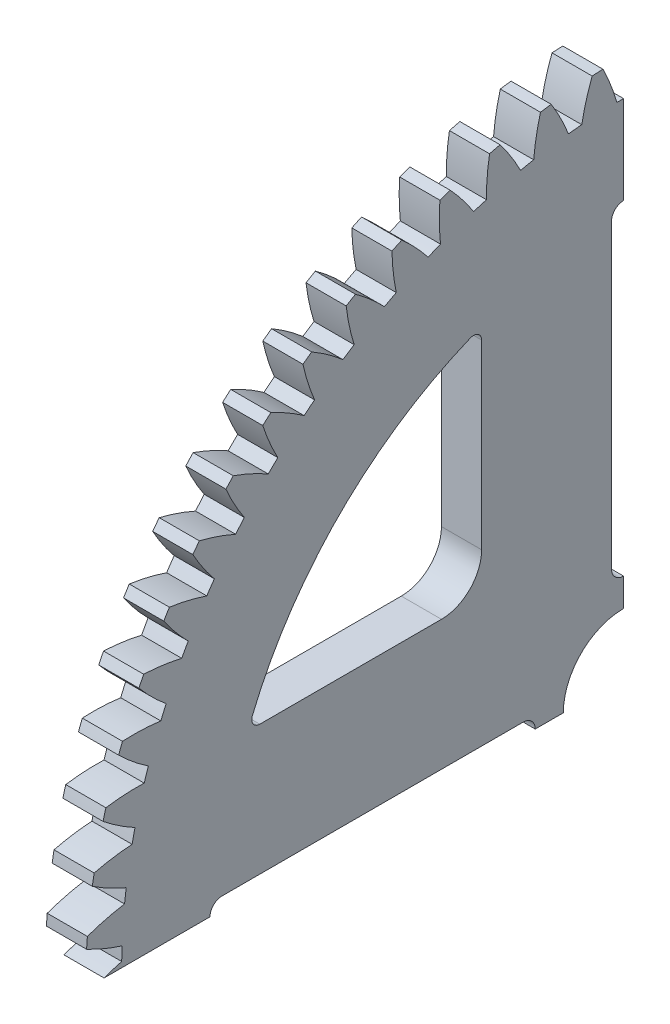
SolidWorks part; units mm, degrees
material "ABS"
ref_plane "Plane1" through (0, 0, 0) normal (0, 0, 1) x (1, 0, 0)
ref_plane "Plane2" through (0, 0, 0) normal (0, 1, 0) x (1, 0, 0)
ref_plane "Plane3" through (0, 0, 0) normal (1, 0, 0) x (0, 0, -1)
sketch "HoldingSke" plane through (0, 0, 0) normal (0, 1, 0) x (1, 0, 0)
  line L0 (0, 0) -> (0.1057, -0.2266)
  line L1 (-15, 0) -> (100, 0) construction
  line L2 (0, 0) -> (-2.1039, 2.3779)
  line L3 (0, 0) -> (-11.863, 4.5341)
  line L4 (0, 0) -> (3.6497, 7.8269)
  line L5 (0, 0) -> (-46.8476, -17.4728)
  line L6 (0, 0) -> (-8.2896, -5.593)
  line L7 (-2.1039, 2.3779) -> (8.6586, 51.2059)
  line L8 (-76.2, 54.61) -> (-74.8, 54.61)
  line L9 (-71.009, 38.7566) -> (-53.1078, 45.2721)
  line L10 (-76.2, 71.12) -> (104.1128, 71.12)
  line L11 (0, 0) -> (-10, 0)
  line L12 (-76.2, 101.6) -> (-76.073, 101.6)
  line L13 (24.9733, 27.94) -> (52.9518, 28.4284)
  line L14 (24.9733, 27.94) -> (24.9743, 27.94)
  line L15 (24.9733, 27.94) -> (100.4006, 29.5858)
  line L16 (-63.627, -4) -> (-12.827, -4)
  circle A0 centre (0, 0) radius 4
  circle A1 centre (0, 0) radius 6
  circle A2 centre (0, 0) radius 6
  circle A3 centre (0, 0) radius 4
  dimension "Num_teeth" = 65
  dimension "Pitch_radius" = 180.3128
  dimension "Width" = 10
  dimension "Thickness" = 10
sketch "BasProSke" plane through (0, 0, 0) normal (0, 1, 0) x (1, 0, 0)
  line L0 (-10, 0) -> (60, 0) construction
  line L1 (0, 0) -> (0, 134)
  line L2 (0, 0) -> (10, 0)
  line L3 (10, 0) -> (10, 134)
  line L4 (10, 134) -> (0, 134)
  dimension "Thickness" = 10
  dimension "Diameter" = 268
revolve "Base-Revolve" add sketch "BasProSke" angle 360 about L0
sketch "TooCutSke" plane through (0, 0, 0) normal (1, 0, 0) x (0, 0, -1)
  line L1 (0, 0) -> (0, 107) construction
  line L2 (0, 0) -> (-3.3635, 129.9565) construction
  line L3 (0, 0) -> (-12.5583, 259.6309) construction
  line L4 (-3.3635, 129.9565) -> (-6.2792, 129.8155) construction
  arc A0 (1.6677, 124.9879) -> (-1.6677, 124.9879) centre (0, 0) ccw
  arc A1 (5.1425, 133.9267) -> (-5.1425, 133.9267) centre (0, 0) ccw
  circle A2 centre (0, 0) radius 130 construction
  circle A3 centre (0, 0) radius 122.16 construction
  arc A4 (-1.6677, 124.9879) -> (-5.1425, 133.9267) centre (-51.6653, 110.6968) ccw
  arc A5 (5.1425, 133.9267) -> (1.6677, 124.9879) centre (51.6653, 110.6968) ccw
extrude "ToothCut" cut sketch "TooCutSke" along normal through all
fillet "Breaks" [suppressed] radius 0.08
fillet "RootFillets" [suppressed] radius 1.001
pattern_circular "TeethCuts" count 65 every 5.538 about axis through (-10, 0, 0) along (1, 0, 0) of "ToothCut", "RootFillets", "Breaks"
sketch "HubNeaOneSke" plane through (0, 0, 0) normal (-1, 0, 0) x (0, 0, 1)
  circle A0 centre (0, 0) radius 6
  dimension "Diameter" = 12
extrude "HubNearOne" add sketch "HubNeaOneSke" along normal blind 40.0001
sketch "HubNeaBotSke" plane through (0, 0, 0) normal (-1, 0, 0) x (0, 0, 1)
  circle A0 centre (0, 0) radius 6
  dimension "Diameter" = 12
extrude "HubNearBoth" [suppressed] add sketch "HubNeaBotSke" along normal blind 20
ref_plane "FarPln" through (10, 0, 0) normal (1, 0, 0) x (0, 0, -1)
sketch "HubFarSke" plane through (10, 0, 0) normal (1, 0, 0) x (0, 0, -1)
  circle A0 centre (0, 0) radius 6
  dimension "Diameter" = 12
extrude "HubFar" [suppressed] add sketch "HubFarSke" along normal blind 20
sketch "BorSke" plane through (0, 0, 0) normal (1, 0, 0) x (0, 0, -1)
  circle A0 centre (0, 0) radius 4
  dimension "Diameter" = 8
extrude "Bore" cut sketch "BorSke" along normal mid plane 100.0001
sketch "KeySke" plane through (0, 0, 0) normal (1, 0, 0) x (0, 0, -1)
  line L0 (-1.5, 0) -> (-1.5, 5.4)
  line L1 (-1.5, 5.4) -> (1.5, 5.4)
  line L2 (1.5, 5.4) -> (1.5, 0)
  line L3 (0, 0) -> (0, 34) construction
  line L4 (-1.5, 0) -> (1.5, 0)
  dimension "Width" = 3
extrude "Keyway" [suppressed] cut sketch "KeySke" along normal mid plane 100.0001
pattern_circular "Keyway2" [suppressed] count 2 every 90 about axis through (-10, 0, 0) along (1, 0, 0)
sketch "Esquisse1" plane through (10, 0, 0) normal (1, 0, 0) x (0, 0, -1)
  line L0 (0, 0) -> (0, 125) construction
  line L1 (100, 3) -> (25, 3)
  line L2 (100, -3) -> (25, -3)
  line L3 (-3, 100) -> (-3, 25)
  line L4 (-3, 25) -> (3, 25)
  line L5 (3, 100) -> (3, 25)
  line L6 (-3, 100) -> (3, 25) construction
  line L7 (-3, 25) -> (3, 100) construction
  line L8 (3, -100) -> (3, -25)
  line L9 (-3, -100) -> (-3, -25)
  line L10 (-100, -3) -> (-25, -3)
  line L11 (-100, 3) -> (-25, 3)
  arc A0 (-3, 25) -> (3, 25) centre (0, 25) ccw
  arc A1 (3, 100) -> (-3, 100) centre (0, 100) ccw
  arc A2 (100, -3) -> (100, 3) centre (100, 0) ccw
  arc A3 (25, 3) -> (25, -3) centre (25, 0) ccw
  arc A4 (-3, -100) -> (3, -100) centre (0, -100) ccw
  arc A5 (3, -25) -> (-3, -25) centre (0, -25) ccw
  arc A6 (-100, 3) -> (-100, -3) centre (-100, 0) ccw
  arc A7 (-25, -3) -> (-25, 3) centre (-25, 0) ccw
  point P3 (0, 62.5)
  point P35 (0, 0)
  dimension "D1" = 25
  dimension "D2" = 75
  dimension "D3" = 6
  dimension "D4" = 4
extrude "Enlèv. mat.-Extru.1" cut sketch "Esquisse1" against normal blind 10 contours L5 A1 L3 L4 | L4 A0 | L1 A3 L2 A2 | L10 A7 L11 A6 | L8 A5 L9 A4
sketch "Esquisse3" plane through (0, 0, 0) normal (-1, 0, 0) x (0, 0, 1)
  line L0 (0, 0) -> (-113, 0) construction
  line L1 (-113, 0) -> (-113, 8) construction
  line L2 (-113, -8) -> (-113, -18)
  line L3 (-113, 8) -> (-12, 8)
  line L4 (-113, 8) -> (-113, 18)
  line L5 (-113, 18) -> (-18, 18)
  line L6 (-12, 8) -> (-12, 12)
  line L7 (-12, -8) -> (-12, -12)
  line L8 (-113, -8) -> (-12, -8)
  line L9 (-113, -18) -> (-18, -18)
  line L10 (8, 113) -> (8, 12)
  line L11 (18, 113) -> (18, 18)
  line L12 (8, 12) -> (12, 12)
  line L13 (8, 113) -> (18, 113)
  line L14 (-8, 113) -> (-8, 12)
  line L15 (-8, 113) -> (-18, 113)
  line L16 (-18, 113) -> (-18, 18)
  line L17 (-8, 12) -> (-12, 12)
  line L18 (113, -8) -> (12, -8)
  line L19 (113, -18) -> (18, -18)
  line L20 (12, -8) -> (12, -12)
  line L21 (113, -8) -> (113, -18)
  line L22 (113, 8) -> (12, 8)
  line L23 (113, 8) -> (113, 18)
  line L24 (113, 18) -> (18, 18)
  line L25 (12, 8) -> (12, 12)
  line L26 (-8, -113) -> (-8, -12)
  line L27 (-18, -113) -> (-18, -18)
  line L28 (-8, -12) -> (-12, -12)
  line L29 (-8, -113) -> (-18, -113)
  line L30 (8, -113) -> (8, -12)
  line L31 (8, -113) -> (18, -113)
  line L32 (18, -113) -> (18, -18)
  line L33 (8, -12) -> (12, -12)
  point P38 (0, 0)
  dimension "D1" = 113
  dimension "D2" = 8
  dimension "D4" = 10
  dimension "D5" = 4
extrude "Enlèv. mat.-Extru.2" cut sketch "Esquisse3" against normal blind 5
fillet "Congé1" radius 10 8 edges at (2.5, -18, -18) (2.5, 18, -18) (2.5, 18, 18) (2.5, -18, 18) (2.5, -12, 12) (2.5, -12, -12) (2.5, 12, 12) (2.5, 12, -12)
fillet "Congé2" radius 2 16 edges at (2.5, 113, -18) (2.5, 113, -8) (2.5, 113, 8) (2.5, 113, 18) (2.5, 18, 113) (2.5, 8, 113) (2.5, -8, 113) (2.5, -18, 113) (2.5, -113, 18) (2.5, -113, 8) (2.5, -113, -8) (2.5, -113, -18) (2.5, -18, -113) (2.5, -8, -113) (2.5, 8, -113) (2.5, 18, -113)
sketch "Esquisse4" plane through (0, 0, 0) normal (-1, 0, 0) x (0, 0, 1)
  line L0 (0, 0) -> (35.3553, 35.3553) construction
  line L1 (35.3553, 35.3553) -> (35.3553, 93.5414)
  line L2 (35.3553, 35.3553) -> (93.5414, 35.3553)
  line L3 (35.3553, -35.3553) -> (93.5414, -35.3553)
  line L4 (35.3553, -35.3553) -> (35.3553, -93.5414)
  line L5 (-35.3553, -35.3553) -> (-35.3553, -93.5414)
  line L6 (-35.3553, -35.3553) -> (-93.5414, -35.3553)
  line L7 (-35.3553, 35.3553) -> (-93.5414, 35.3553)
  line L8 (-35.3553, 35.3553) -> (-35.3553, 93.5414)
  arc A0 (35.3553, 93.5414) -> (93.7151, 34.8925) centre (0, 0) cw
  arc A1 (93.5414, -35.3553) -> (34.8925, -93.7151) centre (0, 0) cw
  arc A2 (-35.3553, -93.5414) -> (-93.7151, -34.8925) centre (0, 0) cw
  arc A3 (-93.5414, 35.3553) -> (-34.8925, 93.7151) centre (0, 0) cw
  point P21 (0, 0)
  dimension "D2" = 4
  dimension "D1" = 50
extrude "Enlèv. mat.-Extru.3" cut sketch "Esquisse4" against normal through all contours A3 L7 L8 | A0 L1 L2 | A1 L3 L4 | A2 L5 L6
fillet "Congé3" radius 10 4 edges at (5, -35.3553, -35.3553) (5, -35.3553, 35.3553) (5, 35.3553, 35.3553) (5, 35.3553, -35.3553)
fillet "Congé4" radius 2 8 edges at (5, -35.3553, -93.5414) (5, -93.5414, -35.3553) (5, -93.5414, 35.3553) (5, -35.3553, 93.5414) (5, 35.3553, 93.5414) (5, 93.5414, 35.3553) (5, 35.3553, -93.5414) (5, 93.5414, -35.3553)
fillet "Congé5" radius 1 48 edges at (0, 8, 61.5) (0, 8.5858, 112.4142) (0, 13, 113) (0, 17.4142, 112.4142) (0, 61.5, 8) (0, 112.4142, 8.5858) (0, 113, 13) (0, 112.4142, 17.4142) (0, 69.5, 18) (0, 20.9289, 20.9289) (0, -61.5, 8) (0, -112.4142, 8.5858) (0, -113, 13) (0, -112.4142, 17.4142) (0, -8, 61.5) (0, -8.5858, 112.4142) (0, -13, 113) (0, -17.4142, 112.4142) (0, -18, 69.5) (0, -20.9289, 20.9289) (0, -61.5, -8) (0, -112.4142, -8.5858) (0, -113, -13) (0, -112.4142, -17.4142) (0, -69.5, -18) (0, -20.9289, -20.9289) (0, -18, -69.5) (0, -17.4142, -112.4142) (0, -13, -113) (0, -8.5858, -112.4142) (0, 61.5, -8) (0, 112.4142, -8.5858) (0, 113, -13) (0, 112.4142, -17.4142) (0, 69.5, -18) (0, 20.9289, -20.9289) (0, 8, -61.5) (0, 8.5858, -112.4142) (0, 13, -113) (0, 17.4142, -112.4142) (0, 10.2887, 10.2887) (0, -10.2887, 10.2887) (0, 18, 69.5) (0, -69.5, 18) (0, -10.2887, -10.2887) (0, -8, -61.5) (0, 10.2887, -10.2887) (0, 18, -69.5)
sketch "Esquisse5" plane through (0, 0, 0) normal (-1, 0, 0) x (0, 0, 1)
  circle A0 centre (0, 0) radius 11
  circle A1 centre (0, 0) radius 6
  dimension "D1" = 22
extrude "Boss.-Extru.1" add sketch "Esquisse5" along normal blind 17
fillet "Congé6" radius 2 1 edges at (0, 0, -11)
sketch "Esquisse6" plane through (-40.0001, 0, 0) normal (-1, 0, 0) x (0, 0, 1)
  line L0 (0, 0) -> (0, 3) construction
  line L1 (-2.6458, 3) -> (2.6458, 3)
  arc A1 (-2.6458, 3) -> (2.6458, 3) centre (0, 0) cw
  point P8 (0, 3)
  circle M2 centre (0, 0) radius 4
  dimension "D1" = 3
extrude "Boss.-Extru.2" add sketch "Esquisse6" against normal blind 30 contours L1 M2
sketch "Esquisse7" plane through (-10.0001, 0, 0) normal (1, 0, 0) x (0, 0, -1)
  circle A0 centre (0, 0) radius 4
extrude "Boss.-Extru.3" add sketch "Esquisse7" along normal up to surface (20.0001 mm away) up to face at (10, -56.8058, 56.8058)
sketch "Esquisse8" plane through (-40.0001, 0, 0) normal (-1, 0, 0) x (0, 0, 1)
  circle A0 centre (0, 0) radius 5.9
  circle A1 centre (0, 0) radius 6
  dimension "D1" = 11.8
  dimension "D2" = 12
extrude "Enlèv. mat.-Extru.4" cut sketch "Esquisse8" against normal blind 23
sketch "Esquisse9" plane through (-10.0001, 0, 0) normal (-1, 0, 0) x (0, 0, 1)
  circle A0 centre (0, 0) radius 15
  dimension "D1" = 30
extrude "Enlèv. mat.-Extru.6" cut sketch "Esquisse9" against normal through all
sketch "Esquisse10" plane through (0, 0, 0) normal (-1, 0, 0) x (0, 0, 1)
  line L0 (0, 0) -> (152.2775, 0) construction
  line L1 (0, 0) -> (0, 162.7916) construction
  line L2 (0, 0) -> (0, 162.7916)
  line L3 (0, 162.7916) -> (-202.7708, 162.7916)
  line L4 (-202.7708, 162.7916) -> (-202.7708, -156.395)
  line L5 (-202.7708, -156.395) -> (150.39, -156.395)
  line L6 (150.39, -156.395) -> (150.39, 0)
  line L7 (150.39, 0) -> (0, 0)
extrude "Enlèv. mat.-Extru.7" cut sketch "Esquisse10" against normal blind 10
equation "' \"Module@HoldingSke\" = 6.35"
equation "' \"Num_teeth@HoldingSke\" = 12"
equation "' \"Ap@HoldingSke\" =  20"
equation "' \"Ap@HoldingSke\" = 20"
equation "' \"Width@HoldingSke\" = 0.5 * 25.4"
equation "' \"Hub_dia@HoldingSke\"= 1 * 25.4"
equation "' \"Hub_dia@HoldingSke\" = 1 * 25.4"
equation "' \"Overall_len@HoldingSke\" = 1.0 * 25.4"
equation "' \"Bore@HoldingSke\" = 0.75 * 25.4"
equation "' \"T_dim@HoldingSke\" = 0.1 * 25.4"
equation "' \"Width@KeySke\" = 0.25 * 25.4"
equation "' \"Show_teeth@HoldingSke\" = 13"
equation "' \"Backlash@HoldingSke\" = 0.009 * 25.4"
equation "' \"Addendum_fac@HoldingSke\" = 1.0"
equation "' \"Dedendum_fac@HoldingSke\" = 1.25"
equation "' \"Dedendum_add@HoldingSke\" = 0.00005 * 25.4"
equation "' \"Clearance_fac@HoldingSke\" = 0.25"
equation "\"Pitch@HoldingSke\" = 1 / \"Module@HoldingSke\""
equation "\"Overcut_dia@TooCutSke\" = (\"Num_teeth@HoldingSke\" + 2 * \"Addendum_fac@HoldingSke\") / \"Pitch@HoldingSke\" + 0.002 * 25.4"
equation "\"Pitch_dia@TooCutSke\" = \"Num_teeth@HoldingSke\" / \"Pitch@HoldingSke\""
equation "\"Base_dia@TooCutSke\" = \"Num_teeth@HoldingSke\" / \"Pitch@HoldingSke\" * cos((\"Ap@HoldingSke\"  * 3.14159265 / 180))"
equation "\"Root_dia@TooCutSke\" = (\"Num_teeth@HoldingSke\" + 2) / \"Pitch@HoldingSke\" - 2 * (\"Addendum_fac@HoldingSke\" + \"Dedendum_fac@HoldingSke\") / \"Pitch@HoldingSke\" - \"Dedendum_add@HoldingSke\" * 2"
equation "\"Half_ang@TooCutSke\" = 180 / \"Num_teeth@HoldingSke\""
equation "\"Half_CT@TooCutSke\" = \"Num_teeth@HoldingSke\" / \"Pitch@HoldingSke\" * sin((3.14159265 / 2 / \"Num_teeth@HoldingSke\")) / 2 - 7 * \"Backlash@HoldingSke\" / 4"
equation "\"Flank_rad@TooCutSke\" = \"Num_teeth@HoldingSke\" / \"Pitch@HoldingSke\" / 5"
equation "\"Radius@RootFillets\" = \"Clearance_fac@HoldingSke\" / \"Pitch@HoldingSke\" + \"Dedendum_add@HoldingSke\""
equation "\"Break_rad@Breaks\" = 0.02 / \"Pitch@HoldingSke\""
equation "\"Thickness@HoldingSke\" = \"Width@HoldingSke\""
equation "\"OAL@HoldingSke\" = \"Thickness@HoldingSke\""
equation "\"MHD@HoldingSke\" = (\"Num_teeth@HoldingSke\" + 2) / \"Pitch@HoldingSke\" - 2 * (\"Addendum_fac@HoldingSke\" + \"Dedendum_fac@HoldingSke\")  / \"Pitch@HoldingSke\" - \"Dedendum_add@HoldingSke\" * 2"
equation "\"MBD@HoldingSke\" = (\"Num_teeth@HoldingSke\" + 2) / \"Pitch@HoldingSke\" - 2 * (\"Addendum_fac@HoldingSke\" + \"Dedendum_fac@HoldingSke\")  / \"Pitch@HoldingSke\" - \"Dedendum_add@HoldingSke\" * 2 - 0.002 * 25.4"
equation "\"MHD@HoldingSke\" = ((sgn( \"MHD@HoldingSke\" - \"Hub_dia@HoldingSke\" )-1)*( \"MHD@HoldingSke\" - \"Hub_dia@HoldingSke\" ))/-2+ \"Hub_dia@HoldingSke\""
equation "\"MBD@HoldingSke\" = ((sgn( \"MBD@HoldingSke\" - \"Bore@HoldingSke\" )-1)*( \"MBD@HoldingSke\" - \"Bore@HoldingSke\" ))/-2+ \"Bore@HoldingSke\""
equation "\"OAL@HoldingSke\" = ((sgn( \"OAL@HoldingSke\" - \"Overall_len@HoldingSke\" )+1)*( \"OAL@HoldingSke\" - \"Overall_len@HoldingSke\" ))/2 + \"Overall_len@HoldingSke\" + 0.000002 * 25.4"
equation "\"Num_teeth@TeethCuts\" = int( \"Show_teeth@HoldingSke\" ) + 1"
equation "\"Num_teeth@TeethCuts\" = ((sgn( \"Num_teeth@TeethCuts\" - \"Num_teeth@HoldingSke\" )-1)*( \"Num_teeth@TeethCuts\" - \"Num_teeth@HoldingSke\" ))/-2+ \"Num_teeth@HoldingSke\""
equation "\"Num_teeth@TeethCuts\" = ((sgn( \"Num_teeth@TeethCuts\" - 2.0)+1)*( \"Num_teeth@TeethCuts\" - 2.0))/2 +2.0"
equation "\"Angle@TeethCuts\" = 360.0 / \"Num_teeth@HoldingSke\""
equation "\"Diameter@BasProSke\" = (\"Num_teeth@HoldingSke\" + 2 * \"Addendum_fac@HoldingSke\") / \"Pitch@HoldingSke\""
equation "\"Thickness@BasProSke\"  = \"Thickness@HoldingSke\""
equation "' \"Fillet_rad@BasProSke\" =  \"Thickness@HoldingSke\" * 0.05"
equation "' \"Fillet_rad@BasProSke\" = \"Thickness@HoldingSke\" * 0.05"
equation "\"MHD@HoldingSke\" = ((sgn( \"MHD@HoldingSke\" - \"Root_dia@TooCutSke\" )-1)*( \"MHD@HoldingSke\" - \"Root_dia@TooCutSke\" ))/-2+ \"Root_dia@TooCutSke\""
equation "\"Diameter@HubNeaOneSke\" = \"MHD@HoldingSke\""
equation "\"Length@HubNearOne\" = \"OAL@HoldingSke\" - \"Thickness@BasProSke\""
equation "\"Diameter@HubNeaBotSke\" = \"MHD@HoldingSke\""
equation "\"Length@HubNearBoth\" = ( \"OAL@HoldingSke\" - \"Thickness@BasProSke\" ) / 2.0"
equation "\"Thickness@FarPln\" = \"Thickness@BasProSke\""
equation "\"Diameter@HubFarSke\" = \"MHD@HoldingSke\""
equation "\"Length@HubFar\" = ( \"OAL@HoldingSke\" - \"Thickness@BasProSke\" ) / 2.0"
equation "\"Diameter@BorSke\" = \"MBD@HoldingSke\""
equation "\"D1@Bore\" = \"OAL@HoldingSke\" * 2.0"
equation "\"D1@Keyway\" = \"OAL@HoldingSke\" * 2.0"
equation "\"Offset@KeySke\" = \"T_dim@HoldingSke\" + \"MBD@HoldingSke\" / 2.0"
